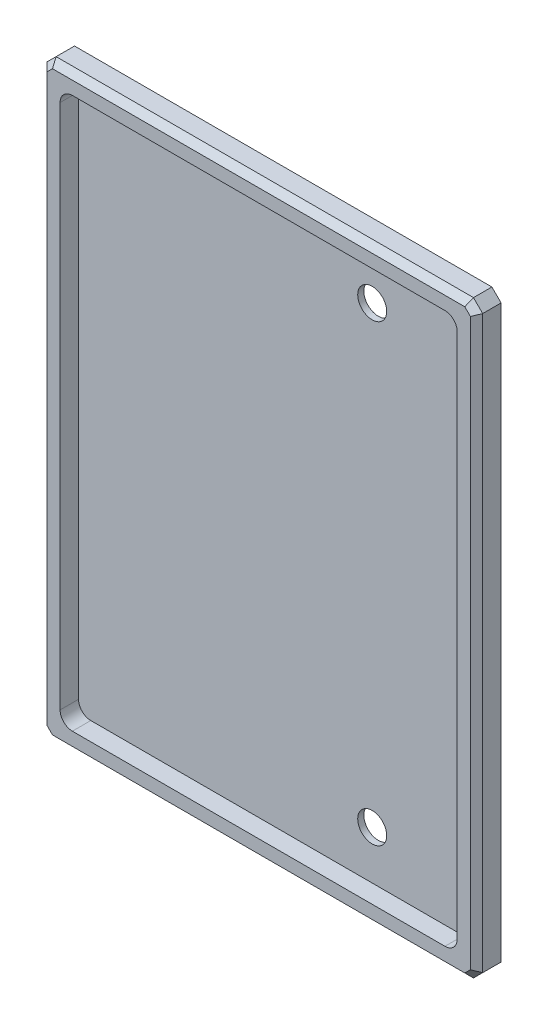
SolidWorks part; units mm, degrees
material "AISI 304"
ref_plane "Front Plane" through (0, 0, 0) normal (0, 0, 1) x (1, 0, 0)
ref_plane "Top Plane" through (0, 0, 0) normal (0, 1, 0) x (1, 0, 0)
ref_plane "Right Plane" through (0, 0, 0) normal (1, 0, 0) x (0, 0, -1)
sketch "Sketch1" plane through (0, 0, 0) normal (0, 0, 1) x (1, 0, 0)
  line L1 (112.7125, -152.4) -> (-112.7125, -152.4)
  line L2 (112.7125, -152.4) -> (112.7125, 152.4)
  line L3 (112.7125, 152.4) -> (-112.7125, 152.4)
  line L4 (-112.7125, -152.4) -> (-112.7125, 152.4)
  line L5 (112.7125, -152.4) -> (-112.7125, 152.4) construction
  line L6 (112.7125, 152.4) -> (-112.7125, -152.4) construction
  point P0 (0, 0)
  dimension "D1" = 304.8
  dimension "D2" = 225.425
extrude "Boss-Extrude1" add sketch "Sketch1" along normal blind 12.7
sketch "Sketch2" plane through (0, 0, 12.7) normal (0, 0, 1) x (1, 0, 0)
  line L0 (-112.7125, 152.4) -> (-112.7125, -152.4) construction
  line L1 (96.3625, -142.4) -> (-96.3625, -142.4)
  line L2 (102.7125, -136.05) -> (102.7125, 136.05)
  line L3 (96.3625, 142.4) -> (-96.3625, 142.4)
  line L4 (-102.7125, -136.05) -> (-102.7125, 136.05)
  line L5 (102.7125, -142.4) -> (-102.7125, 142.4) construction
  line L6 (102.7125, 142.4) -> (-102.7125, -142.4) construction
  line L7 (112.7125, 152.4) -> (-112.7125, 152.4) construction
  arc A0 (-96.3625, -142.4) -> (-102.7125, -136.05) centre (-96.3625, -136.05) cw
  arc A1 (96.3625, -142.4) -> (102.7125, -136.05) centre (96.3625, -136.05) ccw
  arc A2 (102.7125, 136.05) -> (96.3625, 142.4) centre (96.3625, 136.05) ccw
  arc A3 (-96.3625, 142.4) -> (-102.7125, 136.05) centre (-96.3625, 136.05) ccw
  point P0 (0, 0)
  dimension "D3" = 6.35
  dimension "D1" = 10
  dimension "D2" = 10
extrude "Cut-Extrude1" cut sketch "Sketch2" against normal blind 9.525
sketch "Sketch4" plane through (0, 0, 0) normal (0, 0, -1) x (-1, 0, 0)
  line L0 (112.7125, -152.4) -> (-112.7125, -152.4) construction
  line L1 (-112.7125, -152.4) -> (-112.7125, 152.4) construction
  line L2 (0, 0) -> (-117.2439, 0) construction
  circle A0 centre (-49.2125, -117.4) radius 7.5
  circle A1 centre (-49.2125, 117.4) radius 7.5
  dimension "D1" = 15
  dimension "D2" = 35
  dimension "D3" = 63.5
  dimension "D4" = 0
extrude "Cut-Extrude3" cut sketch "Sketch4" against normal through all
hole_wizard "M4x0.7 Tapped Hole1" positions "Sketch10" profile "Sketch11" tap size "M4x0.7" standard "ANSI Metric"
sketch "Sketch10" plane through (0, 0, 0) normal (0, 0, -1) x (-1, 0, 0)
  line L0 (112.7125, 152.4) -> (112.7125, -152.4) construction
  line L1 (-112.7125, 152.4) -> (112.7125, 152.4) construction
  point P0 (109.5375, -113.6)
  point P2 (109.5375, 113.6)
  dimension "D1" = 3.175
  dimension "D2" = 38.8
  dimension "D3" = 266
sketch "Sketch11" plane through (-109.5375, -113.6, 0) normal (1, 0, 0) x (0, 1, 0)
  line L0 (0, 0) -> (0, 6.3914)
  line L1 (0, 6.3914) -> (1.65, 5.4)
  line L2 (1.65, 5.4) -> (1.65, 0)
  line L5 (1.65, 0) -> (0, 0)
  line L10 (0, 6.3914) -> (-1.65, 5.4) construction
  line L11 (0, -6.35) -> (0, 107.95) construction
  dimension "Tap Drill Dia." = 3.3
  dimension "Tap Drill Depth" = 5.4
  dimension "Drill Angle" = 118
cosmetic thread "Hole Thread1" parameters "D1"=3, "D2"=4.3
cosmetic thread "Hole Thread2" parameters "D1"=3, "D2"=4.3
chamfer "Chamfer1" distance 4.7625 angle 45 4 edges at (-112.7125, 152.4, 6.35) (112.7125, 152.4, 6.35) (112.7125, -152.4, 6.35) (-112.7125, -152.4, 6.35)
chamfer "Chamfer2" distance 3.175 angle 45 8 edges at (110.3313, -150.0188, 12.7) (112.7125, 0, 12.7) (110.3313, 150.0187, 12.7) (0, 152.4, 12.7) (-110.3312, 150.0187, 12.7) (-112.7125, 0, 12.7) (-110.3313, -150.0188, 12.7) (0, -152.4, 12.7)
